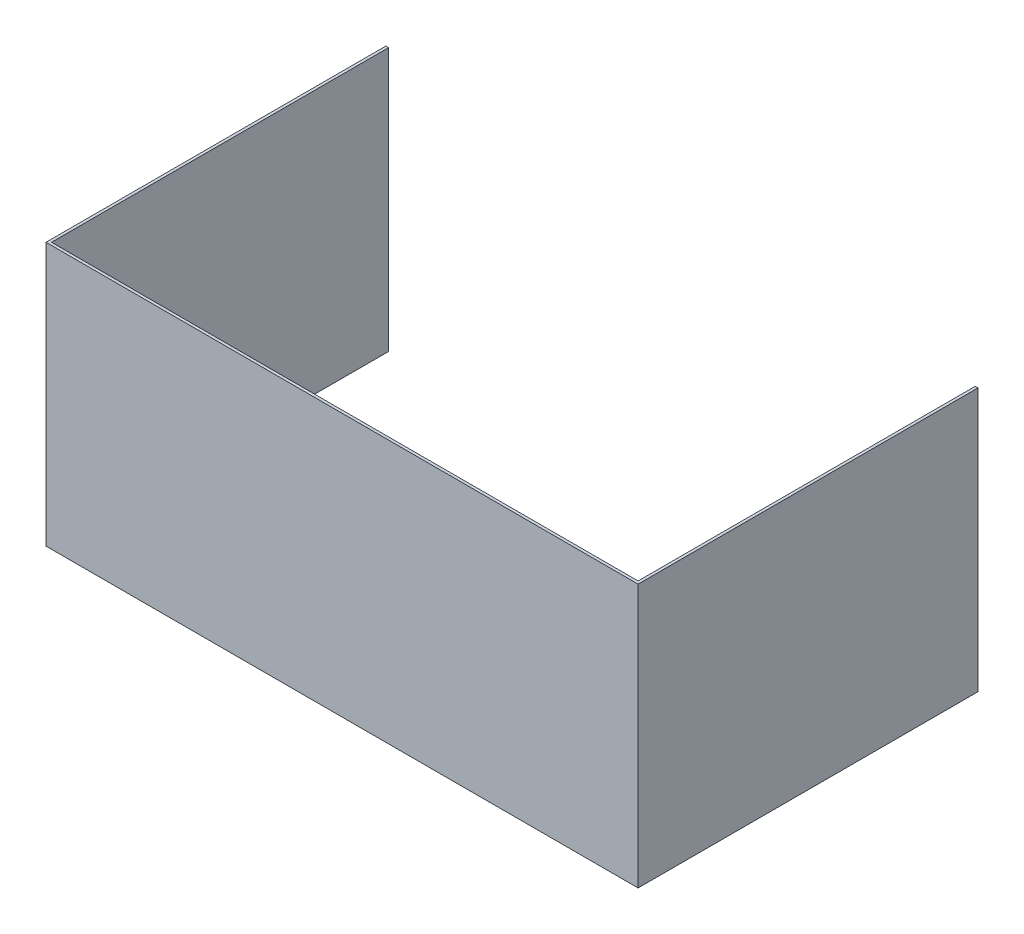
SolidWorks part; units mm, degrees
ref_plane "Front Plane" through (0, 0, 0) normal (0, 0, 1) x (1, 0, 0)
ref_plane "Top Plane" through (0, 0, 0) normal (0, 1, 0) x (1, 0, 0)
ref_plane "Right Plane" through (0, 0, 0) normal (1, 0, 0) x (0, 0, -1)
sketch "Sketch1" plane through (0, 0, 0) normal (0, 1, 0) x (1, 0, 0)
  line L1 (-342.9, -196.85) -> (342.9, -196.85)
  line L2 (-342.9, -196.85) -> (-342.9, 196.85)
  line L4 (342.9, -196.85) -> (342.9, 196.85)
  line L5 (-342.9, -196.85) -> (342.9, 196.85) construction
  line L6 (-342.9, 196.85) -> (342.9, -196.85) construction
  point P0 (0, 0)
  dimension "D1" = 685.8
  dimension "D2" = 393.7
extrude "Extrude-Thin1" add sketch "Sketch1" along normal blind 304.8 thin thin type one direction wall 3.175
